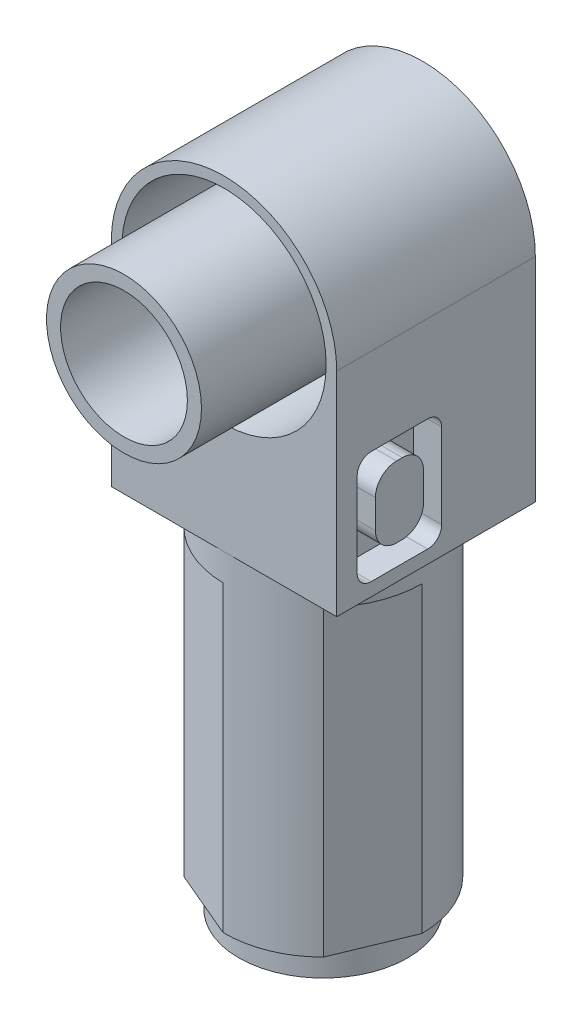
SolidWorks part; units mm, degrees
note: The reader was unsure of these and kept them because the rebuilt part matched: shared geometry of "Sketch12<3>", "Sketch12<4>".
material "Custom Plastic"
ref_plane "X-Y Datum" through (0, 0, 0) normal (0, 0, 1) x (1, 0, 0)
ref_plane "X-Z Datum" through (0, 0, 0) normal (0, 1, 0) x (1, 0, 0)
ref_plane "Y-Z Datum" through (0, 0, 0) normal (1, 0, 0) x (0, 0, -1)
sketch "Sketch1" plane through (0, 0, 0) normal (0, 0, 1) x (1, 0, 0)
  line L0 (0, 8) -> (0, -15.1)
  line L1 (-8, 0) -> (-8, -15.1)
  line L2 (-8, -15.1) -> (8, -15.1)
  line L3 (8, -15.1) -> (8, 0)
  circle A0 centre (0, 0) radius 8
  circle A1 centre (0, 0) radius 4.5
  circle A2 centre (0, 0) radius 5.5
extrude "Boss-Extrude1" add sketch "Sketch1" along normal blind 14.1 contours A0 L0 | A0 L0 L2 L3 | L0 A0 | A0 L1 L2 L0 | A2
sketch "Sketch2" plane through (0, -15.1, 0) normal (0, -1, 0) x (1, 0, 0)
  line L0 (0, 0) -> (0, 14.1)
  line L1 (-8, 14.1) -> (8, 14.1) construction
  line L2 (-8, 7.05) -> (8, 7.05)
  line L3 (-8, 14.1) -> (-8, 0) construction
  line L4 (8, 14.1) -> (8, 0) construction
  circle A0 centre (0, 7.05) radius 7
extrude "Boss-Extrude2" add sketch "Sketch2" along normal blind 2 contours L0 A0 L2 | L2 A0 L0 | L0 A0 L2 | L2 A0 L0
sketch "Sketch3" plane through (0, -17.1, 0) normal (0, -1, 0) x (1, 0, 0)
  line L0 (0, 0) -> (0, 14.1)
  line L1 (-8, 14.1) -> (8, 14.1) construction
  line L2 (-8, 7.05) -> (8, 7.05)
  line L3 (-8, 14.1) -> (-8, 0) construction
  line L4 (8, 14.1) -> (8, 0) construction
  circle A0 centre (0, 7.05) radius 6
  circle A1 centre (0, 7.05) radius 4.5
sketch "Sketch5" plane through (0, 0, 14.1) normal (0, 0, 1) x (1, 0, 0)
  circle A0 centre (0, 0) radius 4.5
  circle A1 centre (0, 0) radius 5.5
sketch "Sketch6" plane through (0, 0, 14.1) normal (0, 0, 1) x (1, 0, 0)
  circle A0 centre (0, 0) radius 7.25
sketch "Sketch8" plane through (0, -17.1, 0) normal (0, -1, 0) x (-1, 0, 0)
  line L0 (0, -7.05) -> (4.9497, -11.9997)
  line L1 (0, -7.05) -> (-4.9497, -11.9997)
  line L2 (0, -7.05) -> (-4.9497, -2.1003)
  line L3 (0, -7.05) -> (4.9497, -2.1003)
  line L4 (4.9497, -11.9997) -> (0, -14.1)
  line L5 (-4.9497, -11.9997) -> (-7, -7.05)
  line L6 (8, -7.05) -> (-8, -7.05) construction
  line L7 (-4.9497, -2.1003) -> (0, 0)
  line L8 (7, -7.05) -> (4.9497, -2.1003)
  circle A0 centre (0, -7.05) radius 7 construction
  circle A1 centre (0, -7.05) radius 7 construction
  arc A2 (7, -7.05) -> (4.9497, -11.9997) centre (0, -7.05) cw
  arc A5 (-7, -7.05) -> (-4.9497, -2.1003) centre (0, -7.05) cw
  arc A6 (4.9497, -2.1003) -> (0, 0) centre (-0.1233, -7.1733) ccw
extrude "Boss-Extrude6" add sketch "Sketch8" along normal blind 21.5
sketch "Sketch9" plane through (0, -38.6, 0) normal (0, -1, 0) x (-1, 0, 0)
  circle A0 centre (0, -7.05) radius 6
  circle A1 centre (0, -7.05) radius 4.5
extrude "Cut-Extrude6" cut sketch "Sketch9" against normal blind 20 contours A1
sketch "Sketch11" plane through (0, -38.6, 0) normal (0, -1, 0) x (-1, 0, 0)
  circle A0 centre (0, -7.05) radius 6
  circle A1 centre (0, -7.05) radius 4.5
extrude "Boss-Extrude8" add sketch "Sketch11" along normal blind 2 contours A0
extrude "Cut-Extrude7" cut sketch "Sketch3" along normal blind 27 contours L2 A1 L0 | L0 A1 L2 | L2 A1 L0 | L0 A1 L2
sketch "Sketch12" plane through (0, 0, 14.1) normal (0, 0, 1) x (1, 0, 0)
  circle A0 centre (0, 0) radius 4.5
  circle A1 centre (0, 0) radius 5.5
  circle A2 centre (0, 0) radius 7.25
extrude "Cut-Extrude8" cut sketch "Sketch12" against normal blind 12 contours A0
extrude "Cut-Extrude9" cut sketch "Sketch12<3>" against normal blind 12 contours A2 A1
sketch "Sketch12<3>" plane through (0, 0, 14.1) normal (0, 0, 1) x (1, 0, 0) same geometry as "Sketch12"
extrude "Boss-Extrude9" add sketch "Sketch12<4>" along normal blind 7.1 contours A1 A0
sketch "Sketch12<4>" plane through (0, 0, 14.1) normal (0, 0, 1) x (1, 0, 0) same geometry as "Sketch12"
sketch "Sketch13" plane through (-8, 0, 0) normal (-1, 0, 0) x (0, 0, 1)
  line L1 (10.9, -6.5162) -> (10.1, -6.5162)
  line L2 (10.9, -6.5162) -> (10.9, -8.7662)
  line L3 (10.9, -8.7662) -> (10.1, -8.7662)
  line L4 (10.1, -6.5162) -> (10.1, -8.7662)
  line L5 (10.9, -6.5162) -> (10.1, -8.7662) construction
  line L6 (10.9, -8.7662) -> (10.1, -6.5162) construction
  line L7 (11.45, -9.6412) -> (12.15, -9.6412)
  line L8 (11.45, -9.6412) -> (11.45, -11.2412)
  line L9 (11.45, -11.2412) -> (12.15, -11.2412)
  line L10 (12.15, -9.6412) -> (12.15, -11.2412)
  line L11 (11.45, -9.6412) -> (12.15, -11.2412) construction
  line L12 (11.45, -11.2412) -> (12.15, -9.6412) construction
  line L13 (8.85, -11.2412) -> (9.55, -11.2412)
  line L14 (8.85, -11.2412) -> (8.85, -9.6412)
  line L15 (8.85, -9.6412) -> (9.55, -9.6412)
  line L16 (9.55, -11.2412) -> (9.55, -9.6412)
  line L17 (8.85, -11.2412) -> (9.55, -9.6412) construction
  line L18 (8.85, -9.6412) -> (9.55, -11.2412) construction
  point P0 (10.5, -7.6412)
  point P5 (11.8, -10.4412)
  point P10 (9.2, -10.4412)
extrude "Cut-Extrude10" cut sketch "Sketch13" against normal blind 2 contours L2 L1 L4 L3 | L14 L13 L16 L15 | L8 L7 L10 L9
sketch "Sketch14" plane through (8, 0, 0) normal (1, 0, 0) x (0, 0, -1)
  line L1 (-7.6475, -14.1659) -> (-11.6475, -14.1659)
  line L2 (-6.6475, -13.1659) -> (-6.6475, -7.1659)
  line L3 (-7.6475, -6.1659) -> (-11.6475, -6.1659)
  line L4 (-12.6475, -13.1659) -> (-12.6475, -7.1659)
  line L5 (-6.6475, -14.1659) -> (-12.6475, -6.1659) construction
  line L6 (-6.6475, -6.1659) -> (-12.6475, -14.1659) construction
  line L7 (-9.4415, -12.6847) -> (-9.8536, -12.6847)
  line L8 (-7.9415, -11.1847) -> (-7.9415, -9.1471)
  line L9 (-9.4415, -7.6471) -> (-9.8536, -7.6471)
  line L10 (-11.3536, -11.1847) -> (-11.3536, -9.1471)
  line L11 (-7.9415, -12.6847) -> (-11.3536, -7.6471) construction
  line L12 (-7.9415, -7.6471) -> (-11.3536, -12.6847) construction
  arc A0 (-11.6475, -14.1659) -> (-12.6475, -13.1659) centre (-11.6475, -13.1659) cw
  arc A1 (-7.6475, -14.1659) -> (-6.6475, -13.1659) centre (-7.6475, -13.1659) ccw
  arc A2 (-7.6475, -6.1659) -> (-6.6475, -7.1659) centre (-7.6475, -7.1659) cw
  arc A3 (-11.6475, -6.1659) -> (-12.6475, -7.1659) centre (-11.6475, -7.1659) ccw
  arc A4 (-9.4415, -7.6471) -> (-7.9415, -9.1471) centre (-9.4415, -9.1471) cw
  arc A5 (-9.4415, -12.6847) -> (-7.9415, -11.1847) centre (-9.4415, -11.1847) ccw
  arc A6 (-11.3536, -11.1847) -> (-9.8536, -12.6847) centre (-9.8536, -11.1847) ccw
  arc A7 (-11.3536, -9.1471) -> (-9.8536, -7.6471) centre (-9.8536, -9.1471) cw
  point P0 (-9.6475, -10.1659)
  point P17 (-9.6475, -10.1659)
  dimension "D1" = 1
  dimension "D2" = 1.5
extrude "Cut-Extrude12" cut sketch "Sketch14" against normal blind 2 contours L2 A2 L3 A3 L4 A0 L1 A1 | L9 A4 L8 A5 L7 A6 L10 A7
